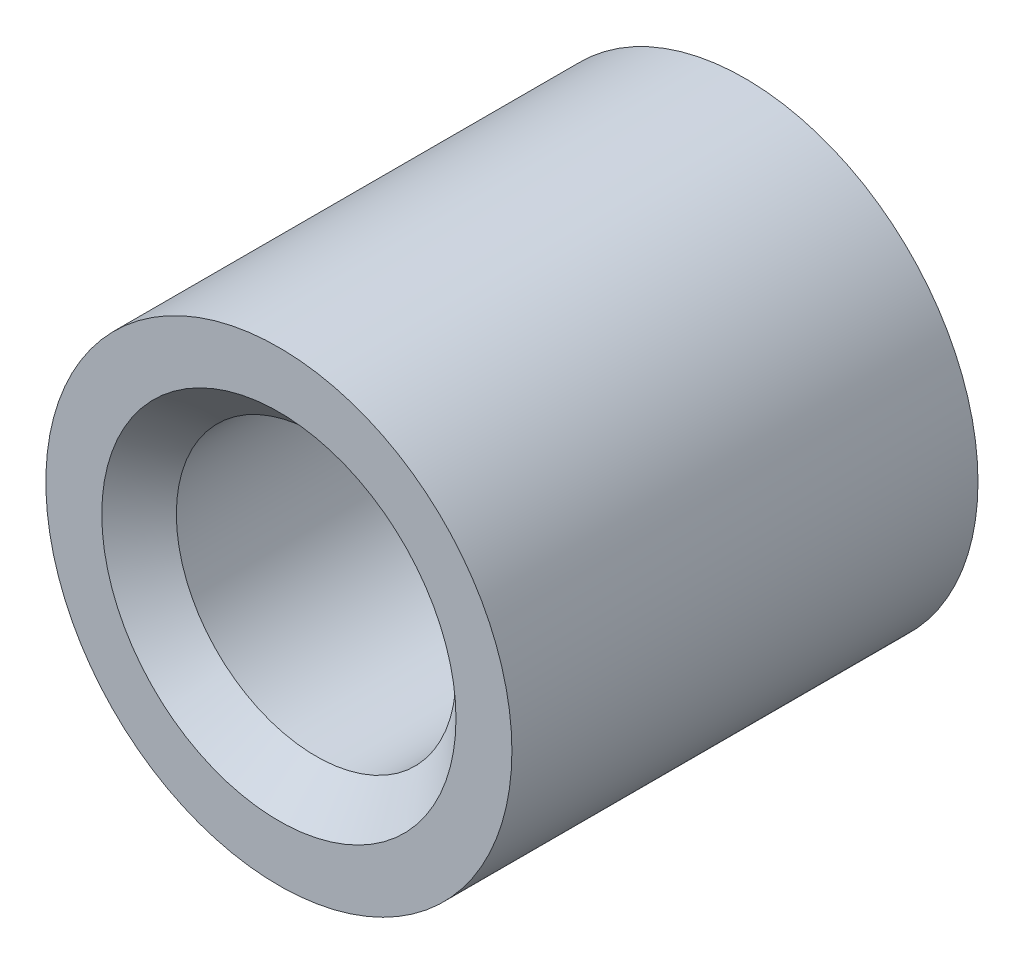
SolidWorks part; units mm, degrees
ref_plane "Front Plane" through (0, 0, 0) normal (0, 0, 1) x (1, 0, 0)
ref_plane "Top Plane" through (0, 0, 0) normal (0, 1, 0) x (1, 0, 0)
ref_plane "Right Plane" through (0, 0, 0) normal (1, 0, 0) x (0, 0, -1)
sketch "Sketch2" plane through (0, 0, 0) normal (0, 0, 1) x (1, 0, 0)
  circle A0 centre (0, 0) radius 4.7625
  circle A1 centre (0, 0) radius 7.9375
  dimension "tube_od" = 15.875
  dimension "tube_id" = 9.525
extrude "tube" add sketch "Sketch2" along normal blind 15.875
chamfer "Chamfer1" distance 1.27 angle 45 2 edges at (4.7625, 0, 0) (4.7625, 0, 15.875)
